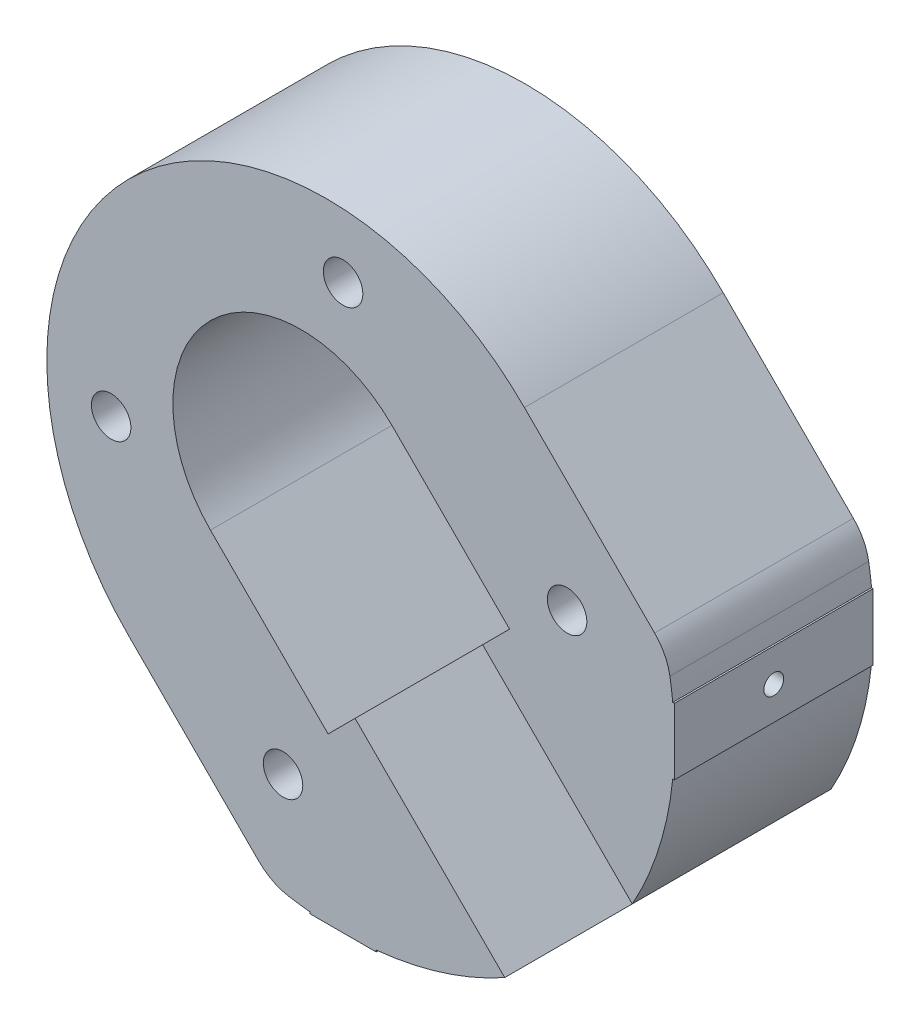
SolidWorks part; units mm, degrees
ref_plane "Front Plane" through (0, 0, 0) normal (0, 0, 1) x (1, 0, 0)
ref_plane "Top Plane" through (0, 0, 0) normal (0, 1, 0) x (1, 0, 0)
ref_plane "Right Plane" through (0, 0, 0) normal (1, 0, 0) x (0, 0, -1)
ref_axis "Z" through (0, 0, 33.5996) along (0, 0, -1)
ref_axis "X" through (56.0652, 0, 0) along (-1, 0, 0)
ref_axis "Y" through (0, -54.2845, 0) along (0, 1, 0)
sketch "Sketch1" plane through (0, 0, 0) normal (0, 0, 1) x (1, 0, 0)
  line L0 (5, -50) -> (-5, -50)
  line L1 (50, 5) -> (50, -5)
  line L2 (56.0652, 0) -> (-1.1166, 0) construction
  line L3 (0, -54.2845) -> (0, 1.1167) construction
  line L4 (61.712, 0) -> (50, 0) construction
  line L5 (0, -50) -> (0, -57.4075) construction
  line L6 (50, -5) -> (49.7494, -5)
  line L7 (5, -49.7494) -> (5, -50)
  line L10 (65.572, -65.572) -> (0, 0) construction
  line L20 (-5, -50) -> (-5, -49.7494)
  line L21 (49.7494, 5) -> (50, 5)
  line L22 (24.3964, -43.6442) -> (1.8103, -21.058)
  line L23 (43.6442, -24.3964) -> (21.058, -1.8103)
  line L25 (1.8103, -21.058) -> (-2.2604, -25.1287)
  line L26 (-2.2604, -25.1287) -> (-20.0175, -7.3715)
  line L27 (21.058, -1.8103) -> (25.1287, 2.2604)
  line L28 (25.1287, 2.2604) -> (7.3715, 20.0175)
  line L29 (-12.6985, -47.012) -> (-32.3444, -27.3661)
  line L30 (47.012, 12.6985) -> (27.3661, 32.3444)
  circle A0 centre (0, 0) radius 50 construction
  circle A1 centre (0, 0) radius 3.535 construction
  arc A2 (49.7494, -5) -> (5, -49.7494) centre (0, 0) cw construction
  arc A6 (49.7494, 5) -> (49.3214, 8.2098) centre (0, 0) ccw
  arc A7 (5, -49.7494) -> (24.3964, -43.6442) centre (0, 0) ccw
  arc A8 (49.7494, -5) -> (43.6442, -24.3964) centre (0, 0) cw
  arc A9 (7.3715, 20.0175) -> (-20.0175, -7.3715) centre (-6.323, 6.323) ccw
  arc A10 (-8.2098, -49.3214) -> (-12.6985, -47.012) centre (-6.8523, -41.1658) cw
  arc A12 (-8.2098, -49.3214) -> (-5, -49.7494) centre (0, 0) ccw
  arc A13 (35.3553, -35.3553) -> (-8.2098, -49.3214) centre (0, 0) ccw construction
  arc A15 (49.3214, 8.2098) -> (47.012, 12.6985) centre (41.1658, 6.8523) ccw
  arc A17 (49.3214, 8.2098) -> (35.3553, -35.3553) centre (0, 0) ccw construction
  arc A18 (27.3661, 32.3444) -> (-32.3444, -27.3661) centre (-2.4891, 2.4891) ccw
  dimension "D1" = 100
  dimension "D2" = 7.07
  dimension "D3" = 10
  dimension "D4" = 45
extrude "Boss-Extrude1" add sketch "Sketch1" against normal blind 15 and the other way blind 15
sketch "Sketch2" plane through (0, -50, 0) normal (0, 1, 0) x (1, 0, 0)
  line L0 (-57.5886, 0) -> (57.5886, 0) construction
  line L1 (0, -20.5521) -> (0, 20.5521) construction
  circle A0 centre (0, 0) radius 1.5
  dimension "D1" = 3
extrude "Cut-Extrude1" cut sketch "Sketch2" along normal blind 24
sketch "Sketch3" plane through (50, 0, 0) normal (1, 0, 0) x (0, 0, -1)
  circle A0 centre (0, 0) radius 1.5
  dimension "D1" = 3
extrude "Cut-Extrude2" cut sketch "Sketch3" against normal blind 24
sketch "Sketch5" plane through (0, 0, 0) normal (0, 0, 1) x (1, 0, 0)
  line L0 (0, 0) -> (0, -67) construction
  dimension "D1" = 67
ref_plane "Vert" through (0, 0, 0) normal (0.7071, 0.7071, 0) x (0, 0, -1)
sketch "Sketch6" plane through (0, 0, 0) normal (0, 0, 1) x (1, 0, 0)
  line L0 (0, 0) -> (-9.0587, -33.8074) construction
  line L1 (0, 0) -> (18.8244, -18.8244) construction
  line L2 (0, -54.2845) -> (0, 1.1167) construction
  line L3 (0, 0) -> (-35, 0) construction
  circle A0 centre (-9.0587, -33.8074) radius 2.9766
  circle A1 centre (-35, 0) radius 2.9766
  circle A2 centre (0, 35) radius 2.9766
  circle A3 centre (33.8074, 9.0587) radius 2.9766
  dimension "D4" = 5.9531
  dimension "D1" = 35
  dimension "D2" = 45
  dimension "D3" = 60
extrude "Cut-Extrude4" cut sketch "Sketch6" along normal through all
equation "\"EyeDiameter\" = 100"
equation "\"BasePlaneDistance\" = \"EyeDiameter\"/2+\"L2Thickness\"+\"EyeClearance\""
equation "\"EyeClearance\" = 2"
equation "\"EyeOD\"= \"EyeDiameter\""
equation "\"D2@Sketch1\"= 7.07"
equation "\"pinHoleDiameter\"= 3"
equation "\"D1@Sketch2\"=\"pinHoleDiameter\""
equation "\"D1@Sketch3\"=\"pinHoleDiameter\""
equation "\"D1@Sketch5\"=\"BasePlaneDistance\""
equation "\"L2_ID\" = 20"
equation "\"vx\" = 0"
equation "\"vy\" = 0"
equation "\"vz\" = 100"
equation "\"parametric_end\" = 1"
equation "\"Rw_3_xx\" = -(\"vz\")/sqr((\"vx\")^2 + (\"vz\")^2)"
equation "\"Rw_3_xy\" = 0"
equation "\"Rw_3_xz\" = (\"vx\")/sqr((\"vx\")^2 + (\"vz\")^2)"
equation "\"Rw_3_zx\" = (\"vx\")/sqr((\"vx\")^2 + (\"vy\")^2 + (\"vz\")^2)"
equation "\"Rw_3_zy\" = (\"vy\")/sqr((\"vx\")^2 + (\"vy\")^2 + (\"vz\")^2)"
equation "\"Rw_3_zz\" = (\"vz\")/sqr((\"vx\")^2 + (\"vy\")^2 + (\"vz\")^2)"
equation "\"Rw_3_yx\" = (\"vx\")*(\"vy\")/sqr((\"vx\")^4 + (\"vx\")^2*(\"vy\")^2 + 2*(\"vx\")^2*(\"vz\")^2 + (\"vy\")^2*(\"vz\")^2 + (\"vz\")^4)"
equation "\"Rw_3_yy\" = -sqr((\"vx\")^2 + (\"vz\")^2)/sqr((\"vx\")^2 + (\"vy\")^2 + (\"vz\")^2)"
equation "\"Rw_3_yz\" = (\"vy\")*(\"vz\")/sqr((\"vx\")^4 + (\"vx\")^2*(\"vy\")^2 + 2*(\"vx\")^2*(\"vz\")^2 + (\"vy\")^2*(\"vz\")^2 + (\"vz\")^4)"
equation "\"O2Targx\" = -\"BasePlaneDistance\"*(\"vx\")*(\"vy\")/sqr((\"vx\")^4 + (\"vx\")^2*(\"vy\")^2 + 2*(\"vx\")^2*(\"vz\")^2 + (\"vy\")^2*(\"vz\")^2 + (\"vz\")^4)"
equation "\"O2Targy\" = \"BasePlaneDistance\"*sqr((\"vx\")^2 + (\"vz\")^2)/sqr((\"vx\")^2 + (\"vy\")^2 + (\"vz\")^2)"
equation "\"O2Targz\" = -\"BasePlaneDistance\"*(\"vy\")*(\"vz\")/sqr((\"vx\")^4 + (\"vx\")^2*(\"vy\")^2 + 2*(\"vx\")^2*(\"vz\")^2 + (\"vy\")^2*(\"vz\")^2 + (\"vz\")^4)"
equation "\"O2Targx_0\" = -(\"BasePlaneDistance\")*sqr((\"vx\")^2 + (\"vz\")^2)/sqr((\"vx\")^2 + (\"vy\")^2 + (\"vz\")^2)"
equation "\"O2Targy_0\" = -(\"BasePlaneDistance\")*(\"vy\")*(\"vz\")/sqr((\"vx\")^4 + (\"vx\")^2*(\"vy\")^2 + 2*(\"vx\")^2*(\"vz\")^2 + (\"vy\")^2*(\"vz\")^2 + (\"vz\")^4)"
equation "\"O2Targz_0\" = (\"BasePlaneDistance\")*(\"vx\")*(\"vy\")/sqr((\"vx\")^4 + (\"vx\")^2*(\"vy\")^2 + 2*(\"vx\")^2*(\"vz\")^2 + (\"vy\")^2*(\"vz\")^2 + (\"vz\")^4) + (\"BasePlaneDistance\")"
equation "\"theta2_s1\" = arcsin(((\"BasePlaneDistance\") - (\"O2Targz_0\"))/(\"BasePlaneDistance\")) + pi"
equation "\"theta2_s2\" = -arcsin(((\"BasePlaneDistance\") - (\"O2Targz_0\"))/(\"BasePlaneDistance\"))"
equation "\"theta1_s1\" = arcsin((\"O2Targy_0\")/((\"BasePlaneDistance\")*cos((\"Theta2\")))) + pi"
equation "\"theta1_s2\" = -arcsin((\"O2Targy_0\")/((\"BasePlaneDistance\")*cos((\"Theta2\"))))"
equation "\"theta1_s3\" = -arccos(-(\"O2Targx_0\")/((\"BasePlaneDistance\")*cos((\"Theta2\")))) + 2*pi"
equation "\"theta1_s4\" = arccos(-(\"O2Targx_0\")/((\"BasePlaneDistance\")*cos((\"Theta2\"))))"
equation "\"Theta1\" = \"theta1_s2\" 'so far, theta1_s1 and theta1_s4 have agreed, and they agree with the sw constraint solver"
equation "\"Theta2\" = \"theta2_s2\""
equation "\"o2_x\" = -(\"BasePlaneDistance\")*cos((\"Theta1\"))*cos((\"Theta2\"))"
equation "\"o2_y\" = -(\"BasePlaneDistance\")*sin((\"Theta1\"))*cos((\"Theta2\"))"
equation "\"o2_z\" = (\"BasePlaneDistance\")*(sin((\"Theta2\")) + 1)"
equation "\"o1_x\" = (\"BasePlaneDistance\")*sin((\"Theta1\"))"
equation "\"o1_y\" = -(\"BasePlaneDistance\")*cos((\"Theta1\"))"
equation "\"o1_z\" = (\"BasePlaneDistance\")"
equation "\"Actuator1_Theta\" = atn(\"vx\"/\"vz\") 'ik solution for the single link joint"
equation "\"Actuator2_Theta\" = \"Theta1\"  'ik solution for the double link joint"
equation "\"MotorBaseThickness\" = 3 "
equation "\"BaseThickness\" = 3 "
equation "\"EncoderToMagnetAirgap\" = 1 'Encoder to magnet airgap"
equation "\"EncoderHeight\" = 1.192  'Height of the encoder"
equation "\"MagnetThickness\" = 0.5  'Magnet thickness"
equation "\"pcb_thickness\" = 1.6  'Thickness of the PCB"
equation "\"pcb_outer_diameter\" = 32 'the OD of the pcb"
equation "\"shaft_diameter\" = 4"
equation "\"L2Thickness\" = 3.75 * \"shaft_diameter\""
equation "\"D1@Cut-Extrude2\"=\"shaft_diameter\"*6"
equation "\"D1@Cut-Extrude1\"=\"shaft_diameter\"*6"
